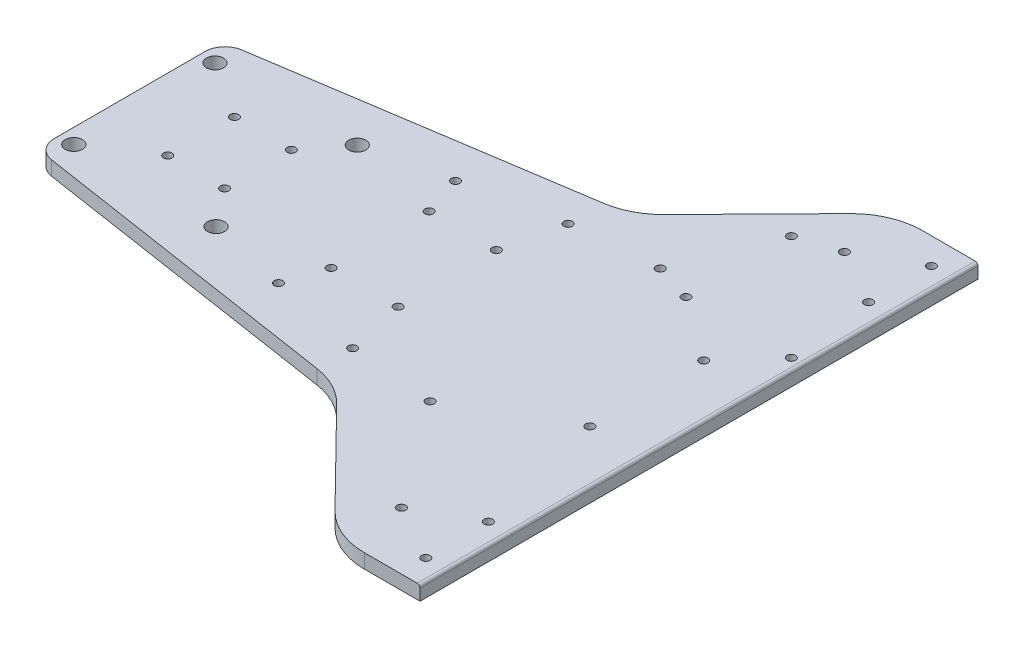
SolidWorks part; units mm, degrees
material "Plastique personnalisé"
ref_plane "Plan de face" through (0, 0, 0) normal (0, 0, 1) x (1, 0, 0)
ref_plane "Plan de dessus" through (0, 0, 0) normal (0, 1, 0) x (1, 0, 0)
ref_plane "Plan de droite" through (0, 0, 0) normal (1, 0, 0) x (0, 0, -1)
sketch "Esquisse1" plane through (0, 0, 0) normal (0, 1, 0) x (1, 0, 0)
  line L0 (0, 0) -> (200, 0) construction
  line L1 (200, -98) -> (200, 98) construction
  line L2 (0, -32.5) -> (0, 32.5) construction
  line L4 (200, 98) -> (180.4869, 98)
  line L5 (162.6514, 90.5184) -> (130.2275, 57.5077)
  line L6 (0, 19.6247) -> (0, -19.6247)
  line L7 (200, 98) -> (200, -98)
  line L8 (200, -98) -> (180.4869, -98)
  line L9 (162.6514, -90.5184) -> (130.2275, -57.5077)
  line L11 (116.1812, -50.3149) -> (0, -32.5)
  line L12 (0, -19.6247) -> (0, -32.5)
  line L13 (116.1812, 50.3149) -> (0, 32.5)
  line L14 (0, 32.5) -> (0, 19.6247)
  arc A0 (116.1812, 50.3149) -> (130.2275, 57.5077) centre (112.392, 75.0261) ccw
  arc A1 (180.4869, 98) -> (162.6514, 90.5184) centre (180.4869, 73) ccw
  arc A3 (180.4869, -98) -> (162.6514, -90.5184) centre (180.4869, -73) cw
  arc A4 (116.1812, -50.3149) -> (130.2275, -57.5077) centre (112.392, -75.0261) cw
  point P13 (170, 98)
  dimension "D5" = 25
  dimension "D1" = 200
  dimension "D2" = 98
  dimension "D3" = 32.5
  dimension "D4" = 30
extrude "Boss.-Extru.1" add sketch "Esquisse1" along normal blind 5
fillet "Congé3" radius 7 2 edges at (0, 2.5, 32.5) (0, 2.5, -32.5)
sketch "Esquisse3" plane through (0, 5, 0) normal (0, 1, 0) x (1, 0, 0)
  circle A0 centre (5.2281, -24.8573) radius 3
  circle A1 centre (5.2281, 24.7436) radius 3
  circle A2 centre (55.2084, -24.8573) radius 3
  circle A3 centre (55.2084, 24.7436) radius 3
  dimension "D1" = 6
  dimension "D2" = 6
  dimension "D3" = 6
  dimension "D4" = 6
extrude "Enlèv. mat.-Extru.1" cut sketch "Esquisse3" against normal blind 5
fillet "Congé2" radius 1 1 edges at (200, 5, 0)
sketch "Esquisse2" plane through (0, 5, 0) normal (0, 1, 0) x (1, 0, 0)
  line L0 (199, 0) -> (-35.8, 0) construction
  line L1 (199, -98) -> (199, 98) construction
ref_axis "Axe1" through (199, 5, 0) along (-1, 0, 0)
sketch "Esquisse4" plane through (0, 5, 0) normal (0, 1, 0) x (1, 0, 0)
  line L0 (199, 0) -> (-81.2291, 0) construction
  circle A0 centre (192.8013, -66.778) radius 1.5038
  circle A1 centre (192.8246, -88.8048) radius 1.4981
  circle A2 centre (173.2691, -77.7914) radius 1.5032
  circle A4 centre (173.2691, 77.7914) radius 1.5032
  circle A5 centre (192.8246, 88.8048) radius 1.4981
  circle A6 centre (192.8013, 66.778) radius 1.5038
extrude "Enlèv. mat.-Extru.2" cut sketch "Esquisse4" against normal blind 10
sketch "Esquisse5" plane through (0, 5, 0) normal (0, 1, 0) x (1, 0, 0)
  line L0 (197.583, 0.0601) -> (146.7238, 0) construction
  line L1 (199, 0) -> (-35.8, 0) construction
  line L2 (181.583, 20.0601) -> (181.6303, -19.9777) construction
  circle A1 centre (223.583, 0.0601) radius 26 construction
  circle A3 centre (181.583, 20.0601) radius 1.5
  circle A4 centre (181.6303, -19.9777) radius 1.5
  dimension "D2" = 40.0377
sketch "Esquisse6" plane through (0, 5, 0) normal (0, 1, 0) x (1, 0, 0)
  circle A0 centre (181.583, 20.0601) radius 1.5
  circle A1 centre (181.6303, -19.9777) radius 1.5
extrude "Enlèv. mat.-Extru.3" cut sketch "Esquisse6" against normal blind 10
sketch "Esquisse7" plane through (0, 5, 0) normal (0, 1, 0) x (1, 0, 0)
  line L0 (-17.0668, 0) -> (188.0366, 0) construction
  line L1 (199, 0) -> (-35.8, 0) construction
  circle A0 centre (145.9493, 40.4145) radius 1.5
  circle A1 centre (145.9493, -40.4145) radius 1.5
extrude "Enlèv. mat.-Extru.4" cut sketch "Esquisse7" against normal blind 10
sketch "Esquisse8" plane through (0, 5, 0) normal (0, 1, 0) x (1, 0, 0)
  circle A0 centre (196.1489, 36.2746) radius 1.5
  circle A2 centre (159.1489, 73.2746) radius 1.5
  circle A3 centre (159.1489, 36.2746) radius 1.5
extrude "Enlèv. mat.-Extru.5" cut sketch "Esquisse8" against normal blind 10
sketch "Esquisse10" plane through (0, 5, 0) normal (0, 1, 0) x (1, 0, 0)
  line L0 (25.0731, 11.7227) -> (45.0731, 11.7227) construction
  line L1 (41.7802, 0) -> (-52.0537, 0) construction
  line L2 (199, 0) -> (-35.8, 0) construction
  line L3 (116.1971, 37.8459) -> (83.3561, 31.0799) construction
  line L4 (99.7766, 34.4629) -> (99.7766, 0) construction
  line L5 (99.7766, 17.2314) -> (111.5606, 17.2314) construction
  circle A0 centre (25.0731, 11.7227) radius 1.5
  circle A1 centre (45.0731, 11.7227) radius 1.5
  circle A2 centre (25.0731, -11.7227) radius 1.5
  circle A3 centre (45.0731, -11.7227) radius 1.5
  circle A4 centre (116.1971, 37.8459) radius 1.5
  circle A5 centre (83.3561, 31.0799) radius 1.5
  circle A6 centre (116.1971, -37.8459) radius 1.5
  circle A7 centre (83.3561, -31.0799) radius 1.5
  circle A10 centre (111.5606, 17.2314) radius 1.5
  circle A11 centre (87.9926, 17.2314) radius 1.5
  circle A12 centre (87.9926, -17.2314) radius 1.5
  circle A13 centre (111.5606, -17.2314) radius 1.5
  dimension "D1" = 20
extrude "Enlèv. mat.-Extru.6" cut sketch "Esquisse10" against normal blind 10
ref_plane "section" through (100, 0, 0) normal (1, 0, 0) x (0, 0, -1)
